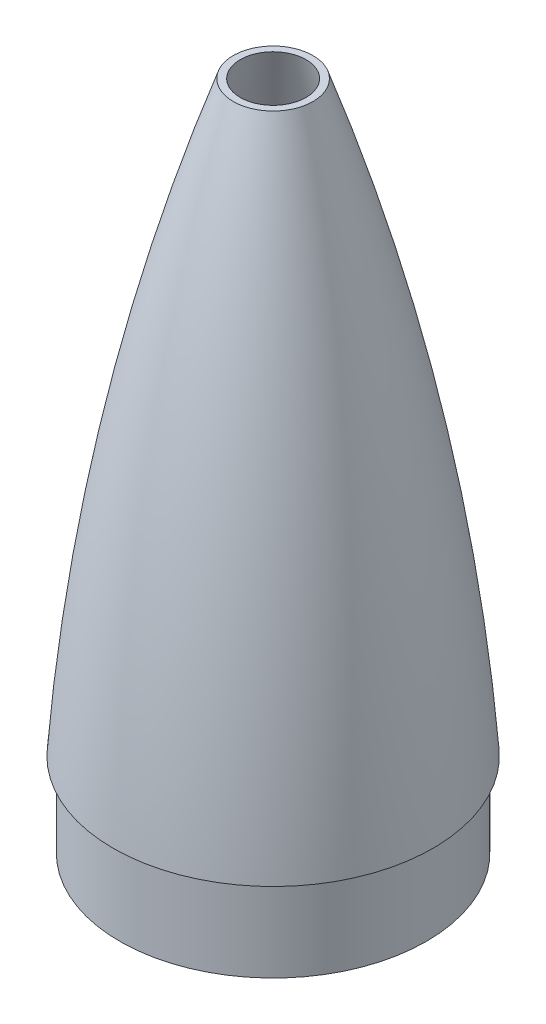
SolidWorks part; units mm, degrees
material "PVB"
ref_plane "Front Plane" through (0, 0, 0) normal (0, 0, 1) x (1, 0, 0)
ref_plane "Top Plane" through (0, 0, 0) normal (0, 1, 0) x (1, 0, 0)
ref_plane "Right Plane" through (0, 0, 0) normal (1, 0, 0) x (0, 0, -1)
sketch "Sketch2" plane through (0, 0, 0) normal (0, 0, 1) x (1, 0, 0)
  line L0 (0, 0) -> (0, 330.2) construction
  line L1 (-76.2, 0) -> (-69.85, 0)
  line L2 (0, 330.2) -> (0, 325.12)
  arc A0 (0, 330.2) -> (-76.2, 0) centre (1014.3906, -77.7824) ccw
  arc A1 (0, 325.12) -> (-69.85, 0) centre (1133.5772, -88.4854) ccw
  dimension "D1" = 330.2
  dimension "D2" = 5.08
  dimension "D3" = 76.2
  dimension "D4" = 6.35
revolve "Revolve1" add sketch "Sketch2" angle 360 about L2
ref_plane "Plane2" through (0, 381, 0) normal (0, 1, 0) x (1, 0, 0)
sketch "Sketch7" plane through (0, 381, 0) normal (0, 1, 0) x (1, 0, 0)
  circle A0 centre (0, 0) radius 317.5
  dimension "D1" = 635
extrude "Cut-Extrude2" cut sketch "Sketch7" against normal blind 101.6
sketch "Sketch8" plane through (0, 0, 0) normal (0, -1, 0) x (1, 0, 0)
  circle A0 centre (0, 0) radius 69.85
  circle A1 centre (0, 0) radius 73.025
  dimension "D1" = 146.05
extrude "Boss-Extrude1" add sketch "Sketch8" along normal blind 40
